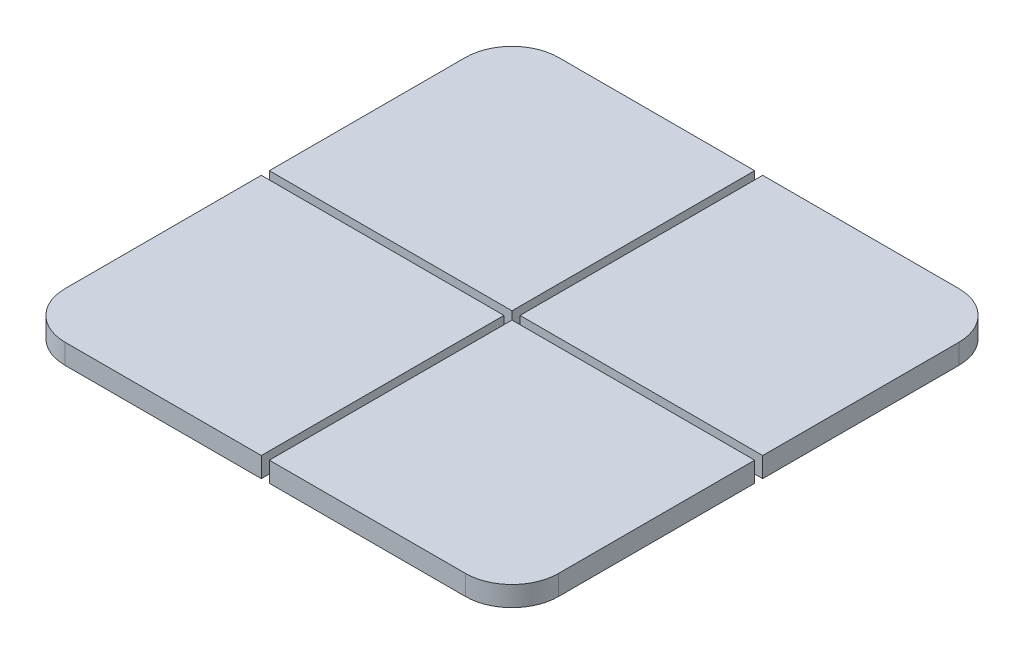
SolidWorks part; units mm, degrees
ref_plane "Front Plane" through (0, 0, 0) normal (0, 0, 1) x (1, 0, 0)
ref_plane "Top Plane" through (0, 0, 0) normal (0, 1, 0) x (1, 0, 0)
ref_plane "Right Plane" through (0, 0, 0) normal (1, 0, 0) x (0, 0, -1)
sketch "Sketch1" plane through (0, 0, 0) normal (0, 1, 0) x (1, 0, 0)
  line L0 (-12.6746, 15.621) -> (12.6746, 15.621)
  line L1 (-12.6746, 15.875) -> (12.6746, 15.875)
  line L2 (-15.875, 12.6746) -> (-15.875, -12.6746)
  line L3 (-12.6746, -15.875) -> (12.6746, -15.875)
  line L4 (15.875, 12.6746) -> (15.875, -12.6746)
  line L5 (0, 15.621) -> (0, -15.621) construction
  line L6 (-15.621, 0) -> (15.621, 0) construction
  line L7 (15.621, 12.6746) -> (15.621, -12.6746)
  line L8 (-12.6746, -15.621) -> (12.6746, -15.621)
  line L9 (-15.621, 12.6746) -> (-15.621, -12.6746)
  line L10 (-15.621, -0.254) -> (15.621, -0.254)
  line L11 (-0.254, 15.621) -> (-0.254, -15.621)
  line L12 (-15.621, 0.254) -> (15.621, 0.254)
  line L13 (0.254, 15.621) -> (0.254, -15.621)
  arc A0 (-15.875, -12.6746) -> (-12.6746, -15.875) centre (-12.6746, -12.6746) ccw
  arc A1 (12.6746, -15.875) -> (15.875, -12.6746) centre (12.6746, -12.6746) ccw
  arc A2 (12.6746, 15.875) -> (15.875, 12.6746) centre (12.6746, 12.6746) cw
  arc A3 (-12.6746, 15.875) -> (-15.875, 12.6746) centre (-12.6746, 12.6746) ccw
  arc A4 (12.6746, 15.621) -> (15.621, 12.6746) centre (12.6746, 12.6746) cw
  arc A5 (12.6746, -15.621) -> (15.621, -12.6746) centre (12.6746, -12.6746) ccw
  arc A6 (-15.621, -12.6746) -> (-12.6746, -15.621) centre (-12.6746, -12.6746) ccw
  arc A7 (-12.6746, 15.621) -> (-15.621, 12.6746) centre (-12.6746, 12.6746) ccw
  point P0 (0, 0)
  point P6 (-15.875, -15.875)
  point P11 (15.875, 15.875)
  point P15 (-15.875, 15.875)
  point P40 (0, 0)
  dimension "D3" = 3.2004
  dimension "D4" = 3.2004
  dimension "D1" = 31.75
  dimension "D2" = 31.75
  dimension "D6" = 0.254
  dimension "D5" = 0.254
  dimension "D7" = 0.254
extrude "Boss-Extrude1" add sketch "Sketch1" against normal blind 1.27 contours L0 A7 L9 L12 L11 | L9 A6 L8 L11 L10 | L8 A5 L7 L10 L13 | A4 L0 L13 L12 L7 region at (-7.8816, 0, -7.8816) region at (7.8816, 0, -7.8816) region at (-7.8816, 0, 7.8816) region at (7.8816, 0, 7.8816)
sketch "Sketch3" plane through (0, 0, 0) normal (0, 1, 0) x (1, 0, 0)
  point P0 (0, 0)
